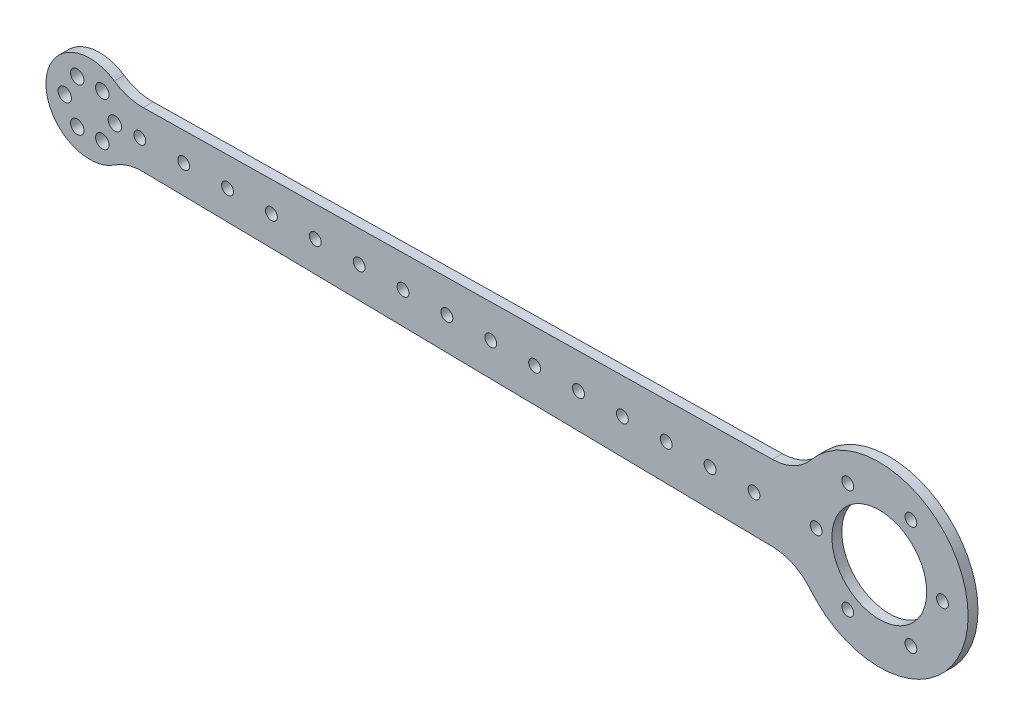
SolidWorks part; units mm, degrees
material "Hexcel AS4C (3000 Filaments)"
ref_plane "Front Plane" through (0, 0, 0) normal (0, 0, 1) x (1, 0, 0)
ref_plane "Top Plane" through (0, 0, 0) normal (0, 1, 0) x (1, 0, 0)
ref_plane "Right Plane" through (0, 0, 0) normal (1, 0, 0) x (0, 0, -1)
sketch "Sketch1" plane through (0, 0, 0) normal (0, 0, 1) x (1, 0, 0)
  line L0 (-100, 0) -> (100, 0) construction
  line L1 (-88.9892, 1.5) -> (77.8859, 4.1495)
  line L2 (-91.3398, 6.9634) -> (79.6881, 9.6788)
  line L3 (-88.9892, -1.5) -> (77.8859, -4.1495)
  line L4 (-91.3398, -6.9634) -> (79.6881, -9.6788)
  line L5 (-100, 0) -> (-100.1083, -6.8242) construction
  line L6 (-100.1083, -6.8242) -> (-91.3398, -6.9634) construction
  line L7 (-91.3398, 6.9634) -> (-100.1083, 6.8242) construction
  line L8 (-100.1083, 6.8242) -> (-100, 0) construction
  line L9 (-88.9892, 1.5) -> (-88.9892, -1.5)
  circle A0 centre (-100, 0) radius 11.1125 construction
  circle A1 centre (100, 0) radius 22.5 construction
  arc A2 (79.6881, 9.6788) -> (79.6881, -9.6788) centre (100, 0) cw
  arc A3 (77.8859, 4.1495) -> (77.8859, -4.1495) centre (100, 0) ccw
  arc A4 (-91.3398, 6.9634) -> (-91.3398, -6.9634) centre (-100, 0) ccw
  point P4 (0, 0)
  point P23 (-88.9892, 0)
  dimension "D2" = 22.225
  dimension "D3" = 45
  dimension "D1" = 200
  dimension "D5" = 5.5
  dimension "D6" = 10
  dimension "D7" = 5.5
  dimension "D4" = 10
  dimension "D8" = 3
extrude "Boss-Extrude1" add sketch "Sketch1" along normal mid plane 2.5
fillet "Fillet1" radius 12.7 4 edges at (79.6881, 9.6788, 0) (79.6881, -9.6788, 0) (-91.3398, -6.9634, 0) (-91.3398, 6.9634, 0)
sketch "Sketch2" plane through (0, 0, 0) normal (0, 0, 1) x (1, 0, 0)
  line L8 (-88.9892, 1.5) -> (-88.9892, -1.5) construction
  line L9 (-88.9892, -1.5) -> (77.8859, -4.1495) construction
  line L10 (77.8859, 4.1495) -> (-88.9892, 1.5) construction
  line L12 (-88.9892, 1.5) -> (-88.9892, -1.5)
  line L13 (-88.9892, -1.5) -> (77.8859, -4.1495)
  line L14 (77.8859, 4.1495) -> (-88.9892, 1.5)
  arc A6 (77.8859, 4.1495) -> (77.8859, -4.1495) centre (100, 0) ccw construction
  arc A7 (77.8859, 4.1495) -> (77.8859, -4.1495) centre (100, 0) ccw
extrude "Boss-Extrude2" add sketch "Sketch2" along normal mid plane 2.5
ref_axis "Axis1" through (100, 0, 1.25) along (0, 0, -1)
ref_axis "Axis2" through (-100, 0, 1.25) along (0, 0, -1)
sketch "Sketch3" plane through (0, 0, 0) normal (0, 0, 1) x (1, 0, 0)
  circle A0 centre (100, 0) radius 12
  dimension "D1" = 24
extrude "Cut-Extrude1" cut sketch "Sketch3" against normal through all both and the other way through all
sketch "Sketch5" plane through (0, 0, 0) normal (0, 0, 1) x (1, 0, 0)
  line L0 (100, 0) -> (116, 0) construction
  circle A0 centre (116, 0) radius 1.5
  dimension "D2" = 3
  dimension "D1" = 16
extrude "Cut-Extrude2" cut sketch "Sketch5" against normal through all both and the other way through all
pattern_circular "CirPattern1" count 6 over 360 about axis through (100, 0, 1.25) along (0, 0, -1) of "Cut-Extrude2"
sketch "Sketch6" plane through (0, 0, 1.25) normal (0, 0, 1) x (1, 0, 0)
  line L0 (100, 0) -> (68.25, 0) construction
  line L1 (-100, 0) -> (-31.7625, 0) construction
  circle A0 centre (68.25, 0) radius 1.5
  circle A1 centre (57.1375, 0) radius 1.5
  circle A2 centre (46.025, 0) radius 1.5
  circle A3 centre (34.9125, 0) radius 1.5
  circle A4 centre (23.8, 0) radius 1.5
  circle A5 centre (12.6875, 0) radius 1.5
  circle A6 centre (1.575, 0) radius 1.5
  circle A7 centre (-9.5375, 0) radius 1.5
  circle A8 centre (-20.65, 0) radius 1.5
  circle A9 centre (-31.7625, 0) radius 1.5
  circle A10 centre (-42.875, 0) radius 1.5
  circle A11 centre (-53.9875, 0) radius 1.5
  circle A12 centre (-65.1, 0) radius 1.5
  circle A13 centre (-76.2125, 0) radius 1.5
  circle A14 centre (-87.325, 0) radius 1.5
  dimension "D1" = 3
  dimension "D2" = 31.75
  dimension "D4" = 11.1125
  dimension "D3" = 15
extrude "Cut-Extrude3" cut sketch "Sketch6" against normal through all both and the other way through all
sketch "Sketch8" plane through (0, 0, 0) normal (0, 0, 1) x (1, 0, 0)
  line L1 (-115, -25.4) -> (-85, -25.4)
  line L2 (-115, -25.4) -> (-115, 25.4)
  line L3 (-115, 25.4) -> (-85, 25.4)
  line L4 (-85, -25.4) -> (-85, 25.4)
  line L5 (-115, -25.4) -> (-85, 25.4) construction
  line L6 (-115, 25.4) -> (-85, -25.4) construction
  point P0 (-100, 0)
  dimension "D1" = 15
  dimension "D2" = 50.8
extrude "Cut-Extrude4" [suppressed] cut sketch "Sketch8" against normal through all both and the other way through all
fillet "Fillet2" [suppressed] radius 2.3813
sketch "Sketch10" [suppressed] plane through (0, 0, 1.25) normal (0, 0, 1) x (1, 0, 0)
  line L0 (-100, 0) -> (-81.825, 0) construction
  line L1 (-85, -4.7688) -> (-85, 4.7688) construction
  line L2 (-81.825, -4) -> (-69.125, -4) construction
  line L3 (-81.825, -4) -> (-81.825, 4) construction
  line L4 (-81.825, 4) -> (-69.125, 4) construction
  line L5 (-69.125, -4) -> (-69.125, 4) construction
  circle A0 centre (-81.825, 4) radius 1.5
  circle A1 centre (-69.125, 4) radius 1.5
  circle A2 centre (-69.125, -4) radius 1.5
  circle A3 centre (-81.825, -4) radius 1.5
  point P8 (-81.825, 0)
  dimension "D4" = 3
  dimension "D1" = 3.175
  dimension "D2" = 12.7
  dimension "D3" = 8
extrude "Cut-Extrude5" [suppressed] cut sketch "Sketch10" against normal through all both and the other way through all
sketch "Sketch11" plane through (0, 0, 0) normal (0, 0, -1) x (-1, 0, 0)
  line L0 (93.65, 0) -> (100, 0) construction
  point P4 (93.65, 0)
  dimension "D2" = 6.35
hole_wizard "M3 Clearance Hole1" positions "Sketch12" profile "Sketch13" hole size "M3" standard "ANSI Metric" end condition up to next
sketch "Sketch12" plane through (0, 0, -1.25) normal (0, 0, -1) x (-1, 0, 0)
  point P0 (93.65, 0)
sketch "Sketch13" plane through (-93.65, 0, -1.25) normal (1, 0, 0) x (0, 1, 0)
  line L0 (0, 0) -> (0, 2.501)
  line L1 (0, 2.501) -> (1.7, 2.501)
  line L2 (1.7, 2.501) -> (1.7, 0)
  line L5 (1.7, 0) -> (0, 0)
  line L11 (0, -6.35) -> (0, 107.95) construction
  dimension "Thru Hole Dia." = 3.4
  dimension "Thru Hole Depth" = 2.501
pattern_circular "CirPattern3" count 6 over 360 about axis through (-100, 0, 1.25) along (0, 0, -1) of "M3 Clearance Hole1" reverse direction yes
equation "\"length\"= 200mm"
equation "\"D1@Sketch1\"=\"length\""
equation "\"Flange_Pulle\"= 45mm"
equation "\"D3@Sketch1\"=\"Flange_Pulle\""
equation "\"C_Upper\"= 10mm"
equation "\"Upper_Thickness\"= 5.5mm"
equation "\"D5@Sketch1\"=\"Upper_Thickness\""
equation "\"C_Lower\"= 10mm"
equation "\"D6@Sketch1\"=\"C_Lower\""
equation "\"Lower_Thickness\"= 5.5mm"
equation "\"D7@Sketch1\"=\"Lower_Thickness\""
equation "\"Foot_Diameter\"=0.875"
equation "\"D2@Sketch1\"=\"Foot_Diameter\""
equation "\"Thicknes\"= 2.5mm"
equation "\"D1@Boss-Extrude1\"=\"Thicknes\""
equation "\"D1@Boss-Extrude2\"=\"Thicknes\""
equation "\"D4@Sketch1\"=\"C_Upper\""
equation "\"m3_clearance\"= 3mm"
equation "\"screw_center_offset\"= 16mm"
equation "\"D2@Sketch5\"=\"m3_clearance\""
equation "\"D1@Sketch5\"=\"screw_center_offset\""
equation "\"D1@Sketch6\"=\"m3_clearance\""
equation "\"I_center_hole_spacing\"=0.4375"
equation "\"D4@Sketch6\"=\"I_center_hole_spacing\""
